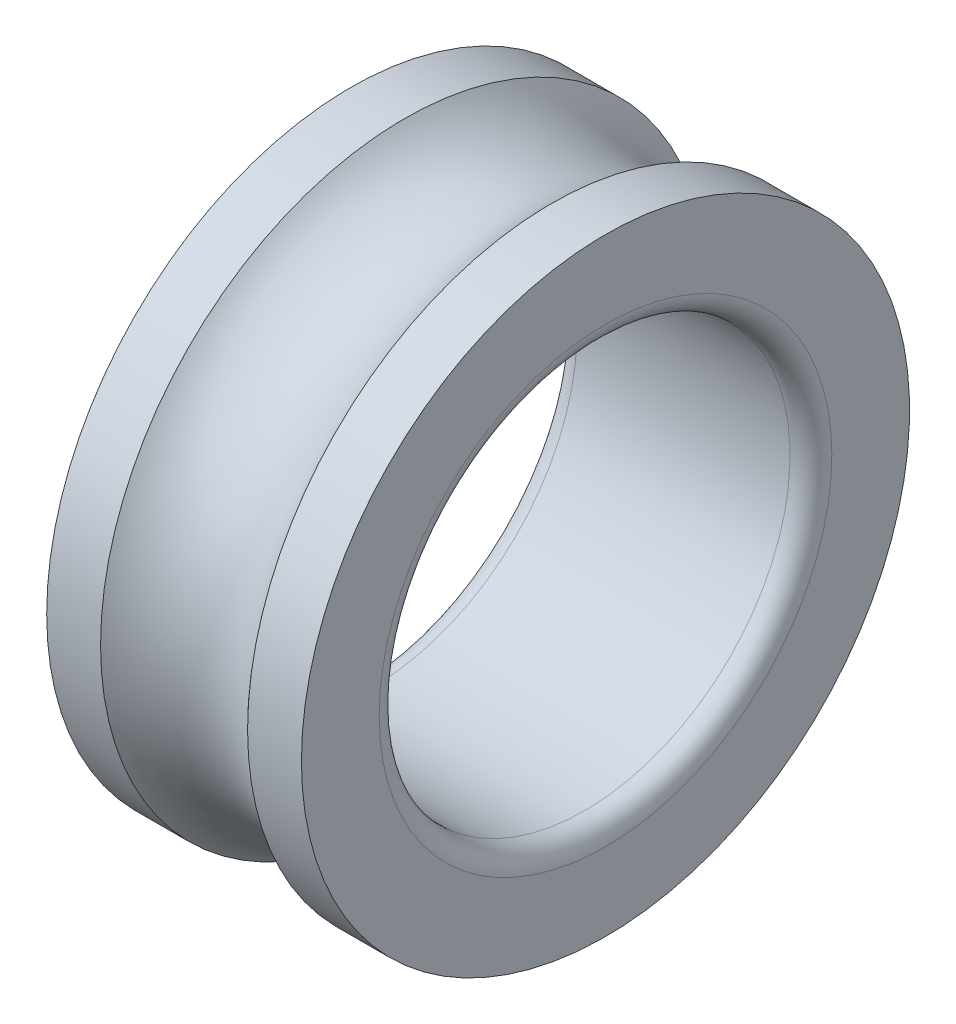
SolidWorks part; units mm, degrees
ref_plane "Front Plane" through (0, 0, 0) normal (0, 0, 1) x (1, 0, 0)
ref_plane "Top Plane" through (0, 0, 0) normal (0, 1, 0) x (1, 0, 0)
ref_plane "Right Plane" through (0, 0, 0) normal (1, 0, 0) x (0, 0, -1)
sketch "Sketch1" plane through (0, 0, 0) normal (0, 0, 1) x (1, 0, 0)
  line L0 (-21.6667, 0) -> (44, 0) construction
  line L1 (0, 25) -> (0, 0) construction
  line L2 (-15.5, 37) -> (-8.9443, 37)
  line L3 (-15.5, 37) -> (-15.5, 27.54)
  line L4 (-12.96, 25) -> (12.96, 25)
  line L5 (15.5, 37) -> (15.5, 27.54)
  line L6 (-15.5, 37) -> (15.5, 25) construction
  line L7 (-15.5, 25) -> (15.5, 37) construction
  line L8 (8.9443, 37) -> (15.5, 37)
  arc A0 (8.9443, 37) -> (-8.9443, 37) centre (0, 45) cw
  arc A1 (-15.5, 27.54) -> (-12.96, 25) centre (-12.96, 27.54) ccw
  arc A2 (12.96, 25) -> (15.5, 27.54) centre (12.96, 27.54) ccw
  point P3 (0, 31)
  dimension "D5" = 12
  dimension "D6" = 2.54
  dimension "D1" = 31
  dimension "D2" = 25
  dimension "D3" = 37
  dimension "D4" = 8
revolve "Revolve1" add sketch "Sketch1" angle 360 about L0
scale "Scale1" scale about centroid uniform scaling yes scale factor 0.19304
